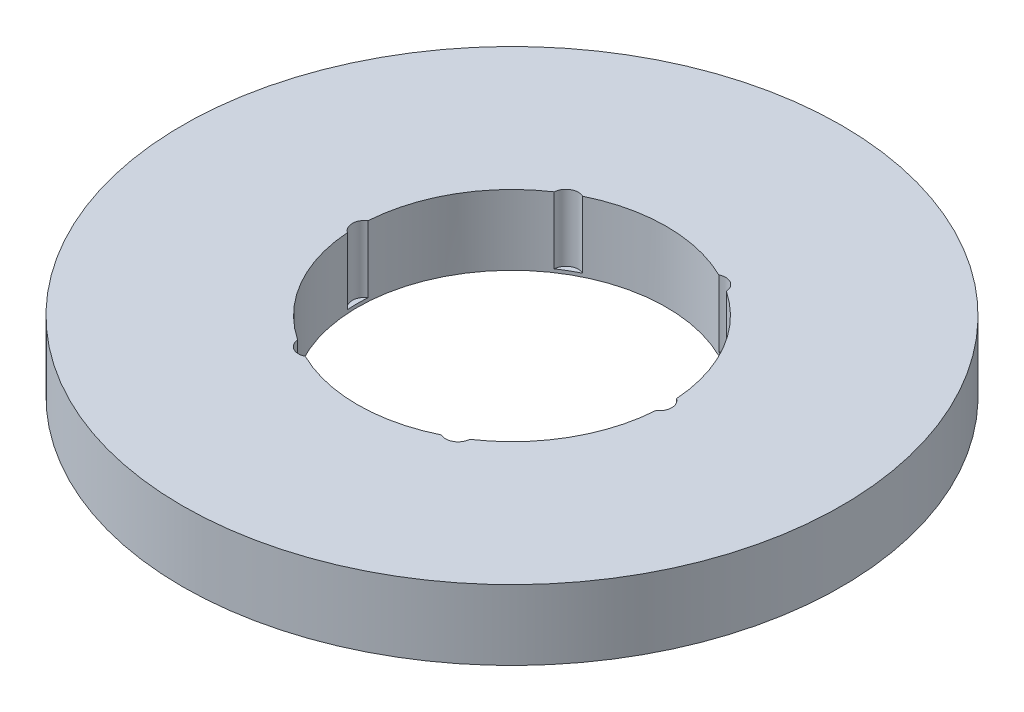
SolidWorks part; units mm, degrees
ref_plane "Front Plane" through (0, 0, 0) normal (0, 0, 1) x (1, 0, 0)
ref_plane "Top Plane" through (0, 0, 0) normal (0, 1, 0) x (1, 0, 0)
ref_plane "Right Plane" through (0, 0, 0) normal (1, 0, 0) x (0, 0, -1)
sketch "Sketch1" plane through (0, 0, 0) normal (0, 1, 0) x (1, 0, 0)
  circle A0 centre (0, 0) radius 80
  dimension "FLANGE_OD" = 160
extrude "Boss-Extrude1" add sketch "Sketch1" along normal blind 17
sketch "Sketch2" plane through (0, 0, 0) normal (0, 1, 0) x (1, 0, 0)
  circle A0 centre (0, 0) radius 37.5
  dimension "BORE_D" = 75
extrude "Cut-Extrude1" cut sketch "Sketch2" along normal through all
sketch "Sketch3" plane through (0, 17, 0) normal (0, 1, 0) x (1, 0, 0)
  circle A0 centre (0, 0) radius 35.7328 construction
  circle A1 centre (-35.7328, 0) radius 3.0281
  dimension "BOLT_D" = 6.0561
  dimension "BOLT_PCD" = 71.4655
extrude "Cut-Extrude2" cut sketch "Sketch3" against normal blind 16.1886
pattern_circular "CirPattern1" count 6 over 360 about axis through (0, 0, 0) along (0, 1, 0) of "Cut-Extrude2"
